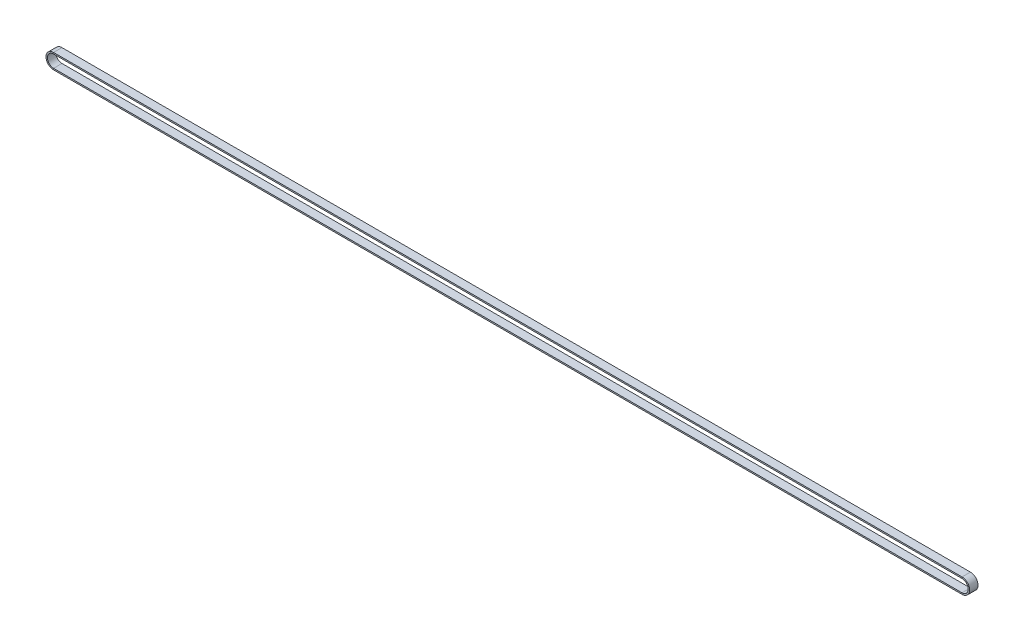
SolidWorks part; units mm, degrees
ref_plane "Front Plane" through (0, 0, 0) normal (0, 0, 1) x (1, 0, 0)
ref_plane "Top Plane" through (0, 0, 0) normal (0, 1, 0) x (1, 0, 0)
ref_plane "Right Plane" through (0, 0, 0) normal (1, 0, 0) x (0, 0, -1)
sketch "Sketch2" plane through (0, 0, 0) normal (0, 0, 1) x (1, 0, 0)
  line L0 (0, 0) -> (1, 0) construction
  line L1 (0, 0) -> (0, 1) construction
  line L2 (-0.0001, 92.1812) -> (-976.331, 92.1812)
  line L3 (-976.331, 108.4607) -> (-0.0001, 108.4607)
  arc A0 (-0.0001, 108.4607) -> (-0.0001, 92.1812) centre (-0.0001, 100.3209) cw
  arc A1 (-976.331, 92.1812) -> (-976.331, 108.4607) centre (-976.331, 100.3209) cw
ref_plane "Plane1" through (-0.0001, 108.4607, 0) normal (1, 0, 0) x (0, 0, -1)
sketch "Sketch3" plane through (-0.0001, 108.4607, 0) normal (1, 0, 0) x (0, 0, -1)
  line L1 (0, -1.5) -> (9, -1.5)
  line L2 (0, -1.5) -> (0, 0)
  line L3 (0, 0) -> (9, 0)
  line L4 (9, -1.5) -> (9, 0)
  dimension "D1" = 1.5
  dimension "D2" = 9
sweep "Sweep1" add profiles "Sketch3" path "Sketch2"
